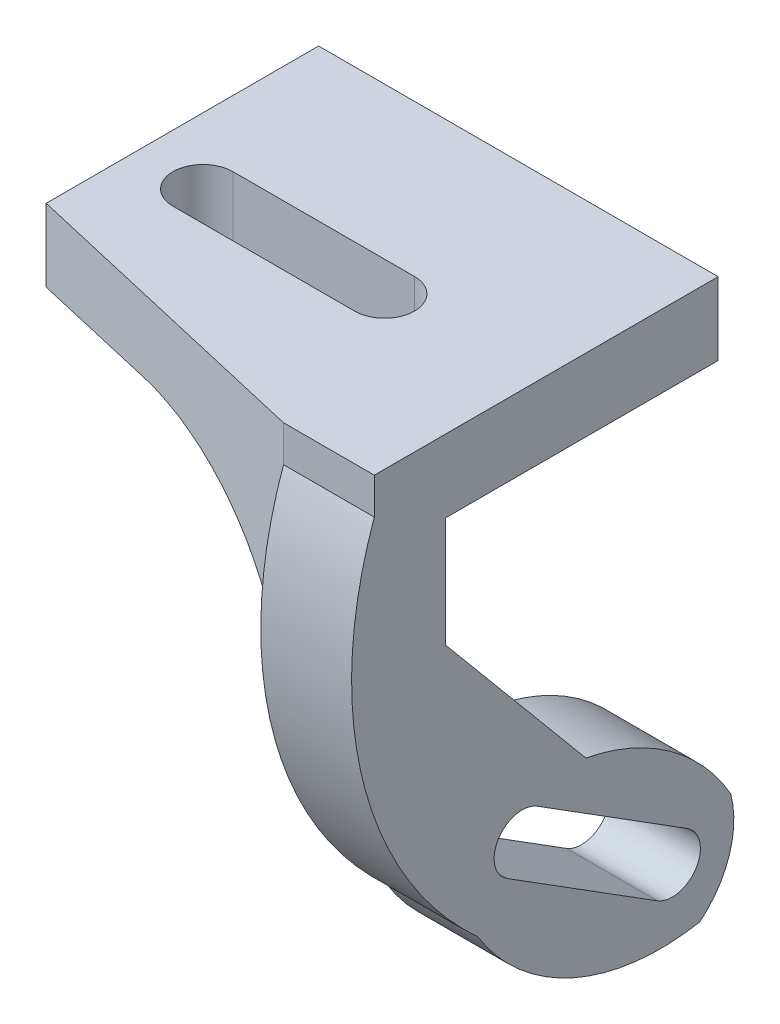
SolidWorks part; units mm, degrees
ref_plane "Ebene vorne" through (0, 0, 0) normal (0, 0, 1) x (1, 0, 0)
ref_plane "Ebene oben" through (0, 0, 0) normal (0, 1, 0) x (1, 0, 0)
ref_plane "Ebene rechts" through (0, 0, 0) normal (1, 0, 0) x (0, 0, -1)
sketch "Skizze2" plane through (0, 0, 0) normal (1, 0, 0) x (0, 0, -1)
  line L0 (0, 0) -> (-15, 0)
  line L1 (0, 0) -> (0, 2)
  line L3 (-18.9315, 2) -> (-18.9315, 4)
  line L4 (-15, -6.0728) -> (-7.2841, -15.3114)
  line L5 (-15, 0) -> (-15, -6.0728)
  line L6 (-15, -6.0728) -> (-18.9315, -6.0728) construction
  line L7 (-18.9315, 4) -> (0, 4)
  line L8 (-2.5268, -22.7754) -> (-10.7869, -17.5833) construction
  line L9 (0, 4) -> (0, 2)
  line L10 (-3.3517, -24.0877) -> (-11.6118, -18.8956)
  line L11 (-1.7019, -21.4631) -> (-9.9621, -16.271)
  arc A0 (0.6932, -21.0041) -> (-1.0078, -26.2653) centre (-4.2298, -22.3181) cw
  arc A1 (-3.3517, -24.0877) -> (-1.7019, -21.4631) centre (-2.5268, -22.7754) ccw
  arc A2 (-9.9621, -16.271) -> (-11.6118, -18.8956) centre (-10.7869, -17.5833) ccw
  arc A3 (0.6932, -21.0041) -> (-7.2841, -15.3114) centre (-9.5156, -26.8741) ccw
  arc A4 (-13.2446, -20.853) -> (-1.0078, -26.2653) centre (-3.1738, -14.6231) ccw
  arc A5 (-18.9315, 2) -> (-13.2446, -20.853) centre (0.9967, -5.175) ccw
  point P13 (-6.6569, -20.1794)
extrude "Aufsatz-Linear austragen1" add sketch "Skizze2" along normal blind 5
sketch "Skizze3" plane through (0, 0, 0) normal (-1, 0, 0) x (0, 0, 1)
  line L0 (15, 2) -> (15, 4)
  line L2 (0, 2) -> (0, 0)
  line L3 (0, 0) -> (15, 0)
  line L4 (15, 2) -> (15, 0)
  line L5 (0, 4) -> (18.9315, 4) construction
  line L6 (15, 4) -> (0, 4)
  line L7 (0, 4) -> (0, 2)
extrude "Aufsatz-Linear austragen2" add sketch "Skizze3" along normal blind 17
sketch "Skizze4" plane through (0, 4, 0) normal (0, 1, 0) x (1, 0, 0)
  line L0 (-3.3683, -10) -> (-13.3683, -10) construction
  line L1 (-3.3683, -11.65) -> (-13.3683, -11.65)
  line L2 (-3.3683, -8.35) -> (-13.3683, -8.35)
  arc A0 (-3.3683, -11.65) -> (-3.3683, -8.35) centre (-3.3683, -10) ccw
  arc A1 (-13.3683, -8.35) -> (-13.3683, -11.65) centre (-13.3683, -10) ccw
  point P4 (-8.3683, -10)
extrude "Schnitt-Linear austragen1" cut sketch "Skizze4" against normal blind 5
sketch "Skizze5" plane through (0, 4, 0) normal (0, 1, 0) x (1, 0, 0)
  line L0 (-17, -15) -> (0, -18.9315)
  line L1 (0, -18.9315) -> (0, -15)
  line L2 (0, -15) -> (-17, -15)
extrude "Aufsatz-Linear austragen3" add sketch "Skizze5" against normal up to surface (4 mm away) up to face at (-8.3683, 0, 10)
fillet "Verrundung2" radius 10 1 edges at (0, 0, 16.9657)
